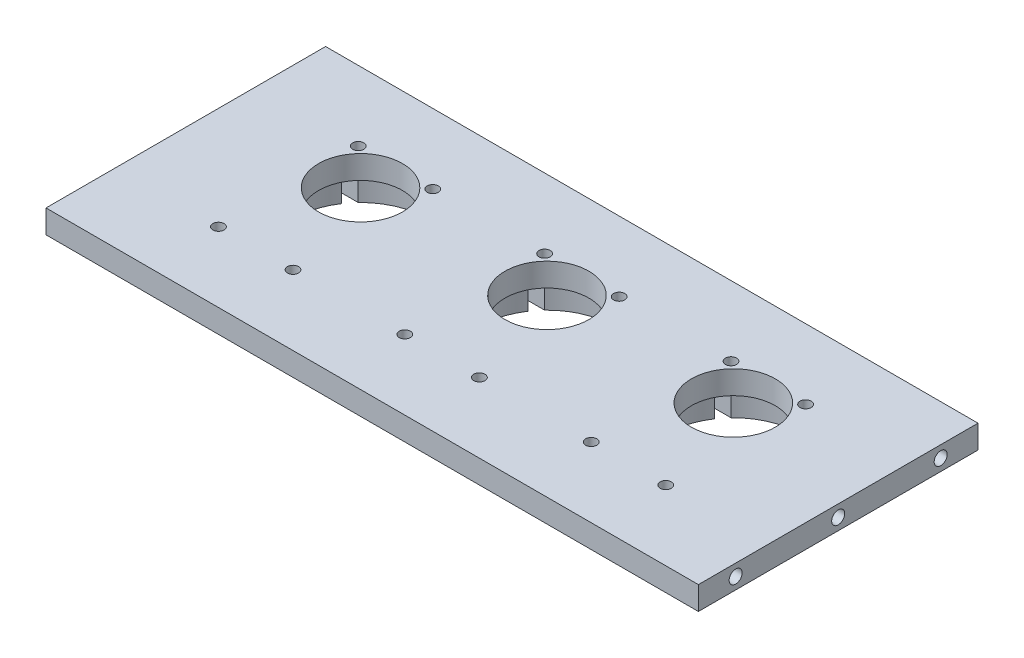
SolidWorks part; units mm, degrees
material "PET"
ref_plane "前视基准面" through (0, 0, 0) normal (0, 0, 1) x (1, 0, 0)
ref_plane "上视基准面" through (0, 0, 0) normal (0, 1, 0) x (1, 0, 0)
ref_plane "右视基准面" through (0, 0, 0) normal (1, 0, 0) x (0, 0, -1)
sketch "草图1" plane through (0, 0, 0) normal (0, 1, 0) x (1, 0, 0)
  line L0 (0, 0) -> (140, 0)
  line L1 (140, 0) -> (140, -60)
  line L2 (140, -60) -> (0, -60)
  line L3 (0, -60) -> (0, 0)
  dimension "D1" = 140
  dimension "D2" = 60
extrude "凸台-拉伸1" add sketch "草图1" along normal blind 5
ref_plane "基准面1" through (0, 0, 30) normal (0, 0, 1) x (1, 0, 0)
sketch "草图2" plane through (0, 5, 0) normal (0, 1, 0) x (1, 0, 0)
  line L0 (140, -30) -> (140, -13) construction
  line L1 (140, -60) -> (140, 0) construction
  line L2 (140, -30) -> (140, -47) construction
  line L3 (0, -13) -> (30, -13) construction
  line L4 (0, 0) -> (0, -60) construction
  line L5 (0, -13) -> (0, -47) construction
  line L6 (0, -47) -> (140, -47) construction
  line L7 (100, -13) -> (120, -13) construction
  line L10 (110, -13) -> (110, -47) construction
  line L11 (102, -15) -> (118, -15) construction
  line L12 (-2.75, -30) -> (2.75, -30) construction
  line L13 (100, -13) -> (140, -13) construction
  circle A0 centre (102, -15) radius 1.2
  circle A1 centre (118, -15) radius 1.2
  circle A2 centre (102, -45) radius 1.2
  circle A3 centre (118, -45) radius 1.2
  circle A4 centre (110, -22.5) radius 9
  point P22 (110, -15)
  point P28 (110, -22.5)
  dimension "D12" = 2.4
  dimension "D13" = 2.4
  dimension "D1" = 17
  dimension "D2" = 17
  dimension "D3" = 140
  dimension "D6" = 20
  dimension "D7" = 20
  dimension "D10" = 16
  dimension "D11" = 15
  dimension "D14" = 9.5
extrude "电机孔位" cut sketch "草图2" against normal through all
ref_plane "基准面2" through (0, 2.5, 0) normal (0, 1, 0) x (1, 0, 0)
ref_axis "基准轴1" through (140, 5, 60) along (0, 0, -1)
ref_axis "基准轴2" through (140, 5, 60) along (0, -1, 0)
ref_point "点1"
sketch "草图4" plane through (0, 0, 0) normal (-1, 0, 0) x (0, 0, 1)
  line L0 (0, 5) -> (0, 0) construction
  line L1 (0, 2.5) -> (60, 2.5) construction
  line L2 (60, 5) -> (60, 0) construction
  line L3 (33, 2.5) -> (-33, 2.5) construction
  line L4 (60, 5) -> (60, 0) construction
  circle A0 centre (30, 2.5) radius 1.4
  circle A1 centre (8, 2.5) radius 1.4
  circle A2 centre (52, 2.5) radius 1.4
  dimension "D1" = 8
  dimension "D2" = 2.8
  dimension "D3" = 2.8
  dimension "D4" = 2.8
  dimension "D5" = 8
extrude "切除-拉伸3" cut sketch "草图4" against normal blind 5
ref_plane "基准面3" through (70, 0, 0) normal (1, 0, 0) x (0, 0, -1)
mirror "镜向1" about plane through (70, 0, 0) normal (1, 0, 0) of "切除-拉伸3"
pattern_linear "阵列(线性)1" count 3 spacing 40 along (-1, 0, 0) of "电机孔位"
sketch "草图5" plane through (0, 0, 0) normal (0, -1, 0) x (1, 0, 0)
  line L1 (30, 13.5) -> (0, 13.5) construction
  line L9 (15.5691, 14.5) -> (17.9066, 14.5)
  line L15 (16.8756, 12.5) -> (19.5, 12.5)
  line L16 (0, 0) -> (0, 60) construction
  line L29 (0, 13.5) -> (0, 14.5) construction
  line L30 (0, 13.5) -> (0, 12.5) construction
  line L31 (3.1, 14.5) -> (15.5691, 14.5)
  line L32 (55.5691, 14.5) -> (57.9066, 14.5)
  line L33 (3.1, 12.5) -> (16.8756, 12.5)
  line L34 (0, 14.5) -> (0, 16.5) construction
  line L35 (3.1, 16.5) -> (14.6296, 16.5)
  line L36 (0, 12.5) -> (0, 10.5) construction
  line L37 (3.1, 10.5) -> (18.6752, 10.5)
  line L38 (40.5, 12.5) -> (43.1244, 12.5)
  line L39 (42.0934, 14.5) -> (44.4309, 14.5)
  line L40 (56.8756, 12.5) -> (59.5, 12.5)
  line L41 (42.0934, 14.5) -> (55.5691, 14.5)
  line L42 (40.5, 12.5) -> (56.8756, 12.5)
  line L44 (45.3704, 16.5) -> (54.6296, 16.5)
  line L46 (41.3248, 10.5) -> (58.6752, 10.5)
  line L47 (80.5, 12.5) -> (83.1244, 12.5)
  line L48 (82.0934, 14.5) -> (84.4309, 14.5)
  line L49 (3.1, 16.5) -> (3.1, 14.5)
  line L50 (3.1, 12.5) -> (3.1, 10.5)
  line L52 (95.5691, 14.5) -> (97.9066, 14.5)
  line L53 (96.8756, 12.5) -> (99.5, 12.5)
  line L54 (82.0934, 14.5) -> (95.5691, 14.5)
  line L55 (80.5, 12.5) -> (96.8756, 12.5)
  line L57 (85.3704, 16.5) -> (94.6296, 16.5)
  line L59 (81.3248, 10.5) -> (98.6752, 10.5)
  line L60 (120.5, 12.5) -> (123.1244, 12.5)
  line L61 (122.0934, 14.5) -> (124.4309, 14.5)
  line L65 (40, 14.5) -> (40, 16.5) [skipped]
  line L66 (40, 13.5) -> (40, 12.5) construction
  line L67 (40, 13.5) -> (40, 14.5) construction
  line L68 (40, 12) -> (40, 10.5) [skipped]
  line L69 (80, 14.5) -> (80, 16.5) [skipped]
  line L70 (80, 13.5) -> (80, 14.5) construction
  line L71 (110, 13.5) -> (80, 13.5) construction
  line L72 (80, 13.5) -> (80, 12.5) construction
  line L73 (70, 13.5) -> (40, 13.5) construction
  line L74 (80, 12) -> (80, 10.5) [skipped]
  arc A13 (19.5, 12.5) -> (40.5, 12.5) centre (30, 22.5) ccw
  arc A16 (34.1231, 14.5) -> (30, 13.5) centre (30, 22.5) ccw construction
  arc A17 (18.6752, 10.5) -> (41.3248, 10.5) centre (30, 22.5) ccw
  arc A18 (45.3704, 16.5) -> (14.6296, 16.5) centre (30, 22.5) ccw
  arc A19 (42.0934, 14.5) -> (17.9066, 14.5) centre (30, 22.5) ccw
  arc A20 (59.5, 12.5) -> (80.5, 12.5) centre (70, 22.5) ccw
  arc A21 (58.6752, 10.5) -> (81.3248, 10.5) centre (70, 22.5) ccw
  arc A22 (85.3704, 16.5) -> (54.6296, 16.5) centre (70, 22.5) ccw
  arc A23 (82.0934, 14.5) -> (57.9066, 14.5) centre (70, 22.5) ccw
  arc A24 (74.1231, 14.5) -> (70, 13.5) centre (70, 22.5) ccw construction
  arc A25 (99.5, 12.5) -> (120.5, 12.5) centre (110, 22.5) ccw
  arc A26 (98.6752, 10.5) -> (123.1244, 12.5) centre (110, 22.5) ccw
  arc A27 (124.4309, 14.5) -> (94.6296, 16.5) centre (110, 22.5) ccw
  arc A28 (122.0934, 14.5) -> (97.9066, 14.5) centre (110, 22.5) ccw
  arc A29 (114.1231, 14.5) -> (110, 13.5) centre (110, 22.5) ccw construction
  line M13 (0, 60) -> (0, 0)
  dimension "D1" = 3
  dimension "D2" = 29
  dimension "D3" = 18
  dimension "D4" = 1
  dimension "D5" = 1
  dimension "D6" = 2
  dimension "D7" = 2
  dimension "D8" = 3.1
extrude "凸台-拉伸5" add sketch "草图5" along normal blind 8 contours A28 L61 A27 L57 A22 L44 A18 L35 L31 L9 A19 L39 L41 L32 A23 L48 L54 L52 M13 | L59 A26 L60 A25 L53 L55 L47 A20 L40 L42 L38 A13 L15 L33 L37 A17 L46 A21 M13 region at (9.3346, 0, 15.7581) region at (18.1878, 0, 11.298)
sketch "草图6" plane through (0, 0, 0) normal (0, -1, 0) x (1, 0, 0)
  circle A0 centre (22, 45) radius 2
  circle A1 centre (38, 45) radius 2
  circle A2 centre (62, 45) radius 2
  circle A3 centre (78, 45) radius 2
  circle A4 centre (102, 45) radius 2
  circle A5 centre (118, 45) radius 2
extrude "切除-拉伸4" cut sketch "草图6" against normal blind 1
